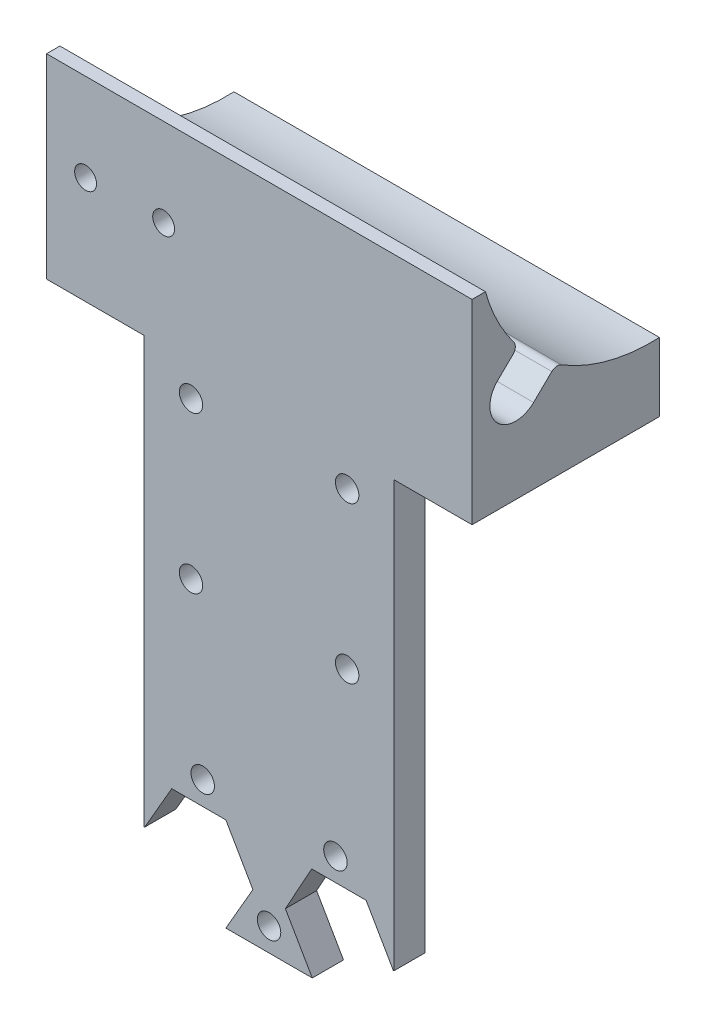
SolidWorks part; units mm, degrees
ref_plane "Front Plane" through (0, 0, 0) normal (0, 0, 1) x (1, 0, 0)
ref_plane "Top Plane" through (0, 0, 0) normal (0, 1, 0) x (1, 0, 0)
ref_plane "Right Plane" through (0, 0, 0) normal (1, 0, 0) x (0, 0, -1)
sketch "Sketch1" plane through (0, 0, 0) normal (0, 0, 1) x (1, 0, 0)
  line L0 (-15, -46.5) -> (15, -46.5) construction
  line L1 (-16, 14) -> (16, 14)
  line L2 (-16, 14) -> (-16, -13.5)
  line L3 (-16, -13.5) -> (16, -13.5)
  line L4 (16, 14) -> (16, -13.5)
  line L5 (-16, -13.5) -> (16, -13.5)
  line L6 (-16, -13.5) -> (-16, -46.5)
  line L7 (-16, -46.5) -> (16, -46.5)
  line L8 (16, -13.5) -> (16, -46.5)
  line L10 (-16, -46.5) -> (-14.9693, -46.5)
  line L11 (-16, -46.5) -> (-16, -13.5)
  line L12 (-16, -13.5) -> (-14.9693, -13.5)
  line L13 (-14.9693, -46.5) -> (-14.9693, -13.5)
  line L14 (15, -46.5) -> (15, -28.5) construction
  line L15 (16, -46.5) -> (15, -46.5)
  line L16 (16, -46.5) -> (16, -13.5)
  line L17 (16, -13.5) -> (15, -13.5)
  line L18 (15, -46.5) -> (15, -13.5)
  line L19 (16, -13.5) -> (-16, -13.5) construction
  line L20 (16, -13) -> (16, -6.5) construction
  line L21 (-16, 13.5) -> (16, 13.5) construction
  line L22 (-16, 14) -> (16, 14) construction
  line L23 (-16, 14) -> (-16, 39)
  line L24 (-16, 39) -> (16, 39)
  line L25 (16, 14) -> (16, 39)
  line L26 (9.5, 20.5152) -> (0, 15.0303)
  line L27 (0, 15.0303) -> (-9.5, 20.5152)
  line L28 (-9.5, 20.5152) -> (-9.5, 31.4848)
  line L29 (-9.5, 31.4848) -> (0, 36.9697)
  line L30 (0, 36.9697) -> (9.5, 31.4848)
  line L31 (9.5, 31.4848) -> (9.5, 20.5152)
  line L32 (9.5, 31.4848) -> (-9.5, 20.5152) construction
  line L33 (-9.5, 31.4848) -> (9.5, 20.5152) construction
  line L34 (0, 15.0303) -> (0, 36.9697) construction
  line L35 (15.9091, -40.467) -> (12.5423, -46.5671)
  line L36 (12.5423, -46.5671) -> (5.5747, -46.5671)
  line L37 (5.5747, -46.5671) -> (2.0909, -40.533)
  line L38 (2.0909, -40.533) -> (5.4577, -34.4329)
  line L39 (5.4577, -34.4329) -> (12.4253, -34.4329)
  line L40 (12.4253, -34.4329) -> (15.9091, -40.467)
  line L41 (12.4253, -34.4329) -> (5.5747, -46.5671) construction
  line L42 (2.0909, -40.533) -> (15.9091, -40.467) construction
  line L43 (12.5423, -46.5671) -> (5.4577, -34.4329) construction
  line L44 (-2.0718, -40.5) -> (-5.5359, -46.5)
  line L45 (-5.5359, -46.5) -> (-12.4641, -46.5)
  line L46 (-12.4641, -46.5) -> (-15.9282, -40.5)
  line L47 (-15.9282, -40.5) -> (-12.4641, -34.5)
  line L48 (-12.4641, -34.5) -> (-5.5359, -34.5)
  line L49 (-5.5359, -34.5) -> (-2.0718, -40.5)
  line L50 (-5.5359, -34.5) -> (-12.4641, -46.5) construction
  line L51 (-15.9282, -40.5) -> (-2.0718, -40.5) construction
  line L52 (-5.5359, -46.5) -> (-12.4641, -34.5) construction
  circle A0 centre (8.5, -31.5) radius 1.5
  circle A1 centre (-8.5, -31.5) radius 1.5
  circle A2 centre (0, -43.5) radius 1.5
  circle A3 centre (-10, -10) radius 1.5
  circle A4 centre (10, -10) radius 1.5
  circle A5 centre (10, 10) radius 1.5
  circle A6 centre (-10, 10) radius 1.5
  circle A7 centre (0, 26) radius 6.1
  point P51 (0, 26)
  point P61 (9, -40.5)
  point P70 (-9, -40.5)
  dimension "D1" = 3
  dimension "D2" = 3
  dimension "D3" = 3
  dimension "D4" = 3
  dimension "D5" = 3
  dimension "D6" = 3
  dimension "D7" = 3
  dimension "D9" = 12.2
  dimension "D10" = 12.5
  dimension "D15" = 27.5
  dimension "D8" = 25
  dimension "D11" = 19
  dimension "D12" = 120
  dimension "D13" = 120
  dimension "D14" = 16
  dimension "D16" = 12
  dimension "D17" = 120
  dimension "D19" = 12
  dimension "D20" = 120
extrude "Boss-Extrude2" add sketch "Sketch1" along normal blind 4 contours L7 L18 L5 L13 A2 A1 A0 | L18 L7 L8 L3 | L4 L1 L2 L3 L5 A6 A5 A4 A3 | L1 L25 L24 L23 L30 L31 L26 L27 L28 L29 | L7 L13 L3 L6 | L31 L30 L29 L28 L27 L26 A7 | A7 region at (-15.5939, 26.5, 0) region at (0, 0.2583, 0) region at (-15.4943, -29.4842, 0) region at (15.5091, -29.5128, 0) region at (0.0089, -25.9534, 0) region at (4.6049, 18.0241, 0) region at (0, 26, 0)
extrude "Boss-Extrude3" add sketch "Sketch1<4>" against normal blind 20 contours L1 L25 L24 L23 L30 L31 L26 L27 L28 L29 | L31 L30 L29 L28 L27 L26 A7 | A7 region at (-15.5939, 26.5, 0) region at (4.6049, 18.0241, 0) region at (0, 26, 0)
sketch "Sketch1<4>" plane through (0, 0, 0) normal (0, 0, 1) x (1, 0, 0) same geometry as "Sketch1"
sketch "Sketch2" plane through (-16, 0, 0) normal (-1, 0, 0) x (0, 0, 1)
  circle A0 centre (-1.58, 25.9998) radius 1.5
  dimension "D3" = 3
extrude "Cut-Extrude3" cut sketch "Sketch2" against normal through all both and the other way through all
sketch "Sketch3" plane through (-16, 0, 0) normal (-1, 0, 0) x (0, 0, 1)
  line L0 (-1.2391, 30.2656) -> (0.717, 28.3692)
  line L1 (0.717, 28.3692) -> (-3.877, 23.6305)
  line L2 (-20, 14) -> (-20, 39) construction
  line L3 (4, 39) -> (-20, 39) construction
  line L4 (2.2876, 39) -> (-20, 39)
  line L5 (-20, 39) -> (-20, 22.7781)
  line L6 (-6.2128, 25.895) -> (-3.877, 23.6305)
  arc A0 (-1.3431, 31.5835) -> (-1.2391, 30.2656) centre (-0.5431, 30.9835) ccw
  arc A1 (0.717, 28.3692) -> (-3.877, 23.6305) centre (-1.58, 25.9998) cw
  arc A2 (-6.2128, 25.895) -> (-7.4329, 26.0287) centre (-6.9089, 25.177) ccw
  arc A3 (-20, 22.7781) -> (-7.4329, 26.0287) centre (-18.9982, 44.8234) ccw
  arc A4 (-26.5932, 24.1035) -> (-7.4329, 26.0287) centre (-18.9982, 44.8234) ccw construction
  arc A5 (-1.3431, 31.5835) -> (2.2876, 39) centre (-18.9982, 44.8234) ccw
  arc A6 (-1.3431, 31.5835) -> (3.0463, 43.8054) centre (-18.9982, 44.8234) ccw construction
  circle M1 centre (-1.58, 25.9998) radius 1.5
  line M2 (4, 39) -> (-20, 39)
  line M3 (-20, 39) -> (-20, 14)
extrude "Cut-Extrude4" cut sketch "Sketch3" against normal blind 5 contours A0 A5 A3 A2 L6 L1 L0 M2 M3 M1 | L1 A1 region at (-16, 31.8175, -10.3816)
extrude "Cut-Extrude5" cut sketch "Sketch3<4>" along normal blind 5 from surface contours A0 A5 A3 A2 L6 L1 L0 M2 M3 M1 | L1 A1 region at (-16, 31.8175, -10.3816) starting at face at (16, 25.9998, -0.08)
sketch "Sketch3<4>" plane through (-16, 0, 0) normal (-1, 0, 0) x (0, 0, 1) same geometry as "Sketch3"
sketch "Sketch5" plane through (0, 0, 4) normal (0, 0, 1) x (1, 0, 0)
  line L0 (17.8253, -40.465) -> (-17.3183, -40.5014)
  line L1 (-17.3183, -40.5014) -> (-17.1295, -46.5)
  line L2 (-17.1295, -46.5) -> (17.9162, -46.5)
  line L3 (17.9162, -46.5) -> (17.8253, -40.465)
  line L4 (-9.5079, -40.4933) -> (-9.5079, -46.5)
  line L5 (-9.5079, -46.5) -> (10.3669, -46.5)
  line L6 (10.3669, -46.5) -> (10.3669, -40.4727)
  line M1 (15, -46.5) -> (16, -46.5)
  line M2 (16, -46.5) -> (16, 39)
  line M4 (-16, 39) -> (-16, -46.5)
  line M5 (-16, -46.5) -> (-14.9693, -46.5)
  line M6 (-14.9693, -46.5) -> (-14.9693, -42.1609)
  line M7 (-14.9693, -42.1609) -> (-15.9282, -40.5)
  line M17 (15.9091, -40.467) -> (15, -42.1142)
  line M18 (15, -42.1142) -> (15, -46.5)
extrude "Cut-Extrude6" cut sketch "Sketch5" against normal through all contours L0 M7 M4 M5 M6 | L6 L2 L0 M18 M17 | L0 M2 M17 M18 M1 | L2 L3 L0 M2 region at (12.7521, -43.4208, 4) region at (15.5279, -43.8331, 4) region at (16.9356, -43.5074, 4) region at (-15.5136, -43.8616, 4)
sketch "Sketch8" plane through (-16, 0, 0) normal (-1, 0, 0) x (0, 0, 1)
  line L0 (-1.2391, 30.2656) -> (0.717, 28.3692)
  line L1 (-3.877, 23.6305) -> (-6.2128, 25.895)
  line L2 (-20, 22.7781) -> (-20, 14)
  line L3 (-20, 14) -> (4, 14)
  line L4 (4, 39) -> (4, -40.5001) construction
  line L5 (4, 14) -> (4, 39)
  line L6 (4, 39) -> (2.2876, 39)
  line L7 (2.2876, 39) -> (-20, 39)
  line L8 (-20, 39) -> (-20, 22.7781)
  arc A0 (2.2876, 39) -> (-1.3431, 31.5835) centre (-18.9982, 44.8234) cw
  arc A1 (-1.3431, 31.5835) -> (-1.2391, 30.2656) centre (-0.5431, 30.9835) ccw
  arc A2 (0.717, 28.3692) -> (-3.877, 23.6305) centre (-1.58, 25.9998) cw
  arc A3 (-6.2128, 25.895) -> (-7.4329, 26.0287) centre (-6.9089, 25.177) ccw
  arc A4 (-7.4329, 26.0287) -> (-20, 22.7781) centre (-18.9982, 44.8234) cw
  circle A5 centre (-1.58, 25.9998) radius 2.574
  arc A6 (-1.3431, 31.5835) -> (-7.4329, 26.0287) centre (-18.9982, 44.8234) cw
  line M3 (4, -40.5001) -> (4, 39)
  line M4 (4, 39) -> (2.2876, 39)
  arc M5 (2.2876, 39) -> (-1.3431, 31.5835) centre (-18.9982, 44.8234) cw
  arc M6 (-1.3431, 31.5835) -> (-1.2391, 30.2656) centre (-0.5431, 30.9835) ccw
  line M7 (-1.2391, 30.2656) -> (0.717, 28.3692)
  arc M8 (0.717, 28.3692) -> (-3.877, 23.6305) centre (-1.58, 25.9998) cw
  line M9 (-3.877, 23.6305) -> (-6.2128, 25.895)
  arc M10 (-6.2128, 25.895) -> (-7.4329, 26.0287) centre (-6.9089, 25.177) ccw
  arc M11 (-7.4329, 26.0287) -> (-20, 22.7781) centre (-18.9982, 44.8234) cw
  line M12 (-20, 22.7781) -> (-20, 14)
  line M13 (-20, 14) -> (0, 14)
extrude "Boss-Extrude5" add sketch "Sketch8" along normal blind 12.5 contours L3 M13 M3 M4 M5 M6 M7 M8 M9 M10 M11 M12 region at (-16, 21.159, -6.0848)
sketch "Sketch7" plane through (0, 0, 4) normal (0, 0, 1) x (1, 0, 0)
  line L1 (-28.5, 39) -> (-8.5, 39)
  line L2 (-28.5, 39) -> (-28.5, 16.5)
  line L3 (-28.5, 16.5) -> (-8.5, 16.5)
  line L4 (-8.5, 39) -> (-8.5, 16.5)
  line L6 (-28.5, 14) -> (-28.5, 39) construction
  line L7 (-28.5, 39) -> (16, 39) construction
  circle A0 centre (-23.5, 27.75) radius 1.4
  circle A1 centre (-13.5, 27.75) radius 1.4
  dimension "D3" = 2.8
  dimension "D4" = 2.8
  dimension "D6" = 11.25
  dimension "D7" = 15
  dimension "D9" = 0
  dimension "D1" = 22.5
  dimension "D2" = 11.25
  dimension "D5" = 5
  dimension "D8" = 0
  dimension "D10" = 5
extrude "Cut-Extrude7" cut sketch "Sketch7" against normal up to surface (2.7824 mm away) contours A0 | A1 region at (-23.5, 27.75, 4) up to face at (-19.75, 24.8513, -0.3954)
extrude "Boss-Extrude6" add sketch "Sketch8<3>" against normal blind 10 from surface contours L3 M13 M3 M4 M5 M6 M7 M8 M9 M10 M11 M12 region at (-16, 21.159, -6.0848) starting at face at (16, 16.1841, -3.5664)
sketch "Sketch8<3>" plane through (-16, 0, 0) normal (-1, 0, 0) x (0, 0, 1) same geometry as "Sketch8"
extrude "Cut-Extrude8" cut sketch "Sketch8<4>" against normal through all contours A6 L7 L8 M5 M11 region at (-16, 32.159, -10.9425)
sketch "Sketch8<4>" plane through (-16, 0, 0) normal (-1, 0, 0) x (0, 0, 1) same geometry as "Sketch8"
